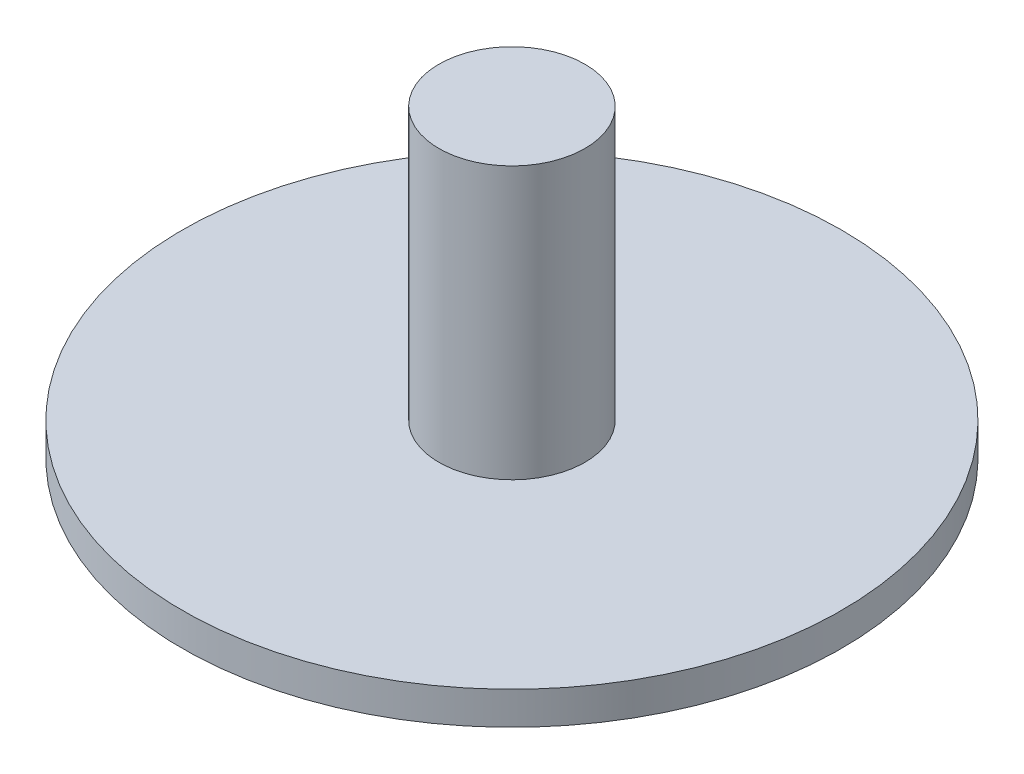
SolidWorks part; units mm, degrees
material "PS HI"
ref_plane "Front Plane" through (0, 0, 0) normal (0, 0, 1) x (1, 0, 0)
ref_plane "Top Plane" through (0, 0, 0) normal (0, 1, 0) x (1, 0, 0)
ref_plane "Right Plane" through (0, 0, 0) normal (1, 0, 0) x (0, 0, -1)
sketch "Sketch1" plane through (0, 0, 0) normal (1, 0, 0) x (0, 0, -1)
  line L0 (0, 0) -> (5.5407, 11.8821)
  line L1 (0, 0) -> (0, 40)
  line L2 (0, 55) -> (0, -55) construction
  line L3 (0, 40) -> (5.5407, 40)
  line L4 (5.5407, 40) -> (5.5407, 19.3821)
  line L5 (5.5407, 19.3821) -> (25, 19.3821)
  line L6 (25, 19.3821) -> (25, 16.8821)
  line L7 (25, 16.8821) -> (5.5407, 16.8821)
  line L8 (5.5407, 16.8821) -> (5.5407, 11.8821)
  dimension "D1" = 40
  dimension "D2" = 25
  dimension "D3" = 25
  dimension "D4" = 2.5
  dimension "D5" = 20.6179
  dimension "D6" = 5
revolve "Revolve1" add sketch "Sketch1" angle 360 about L1
fillet "Fillet1" radius 25 1 edges at (0, 16.8821, -5.5407)
fillet "Fillet11" radius 25 1 edges at (0, 11.8821, -5.5407)
